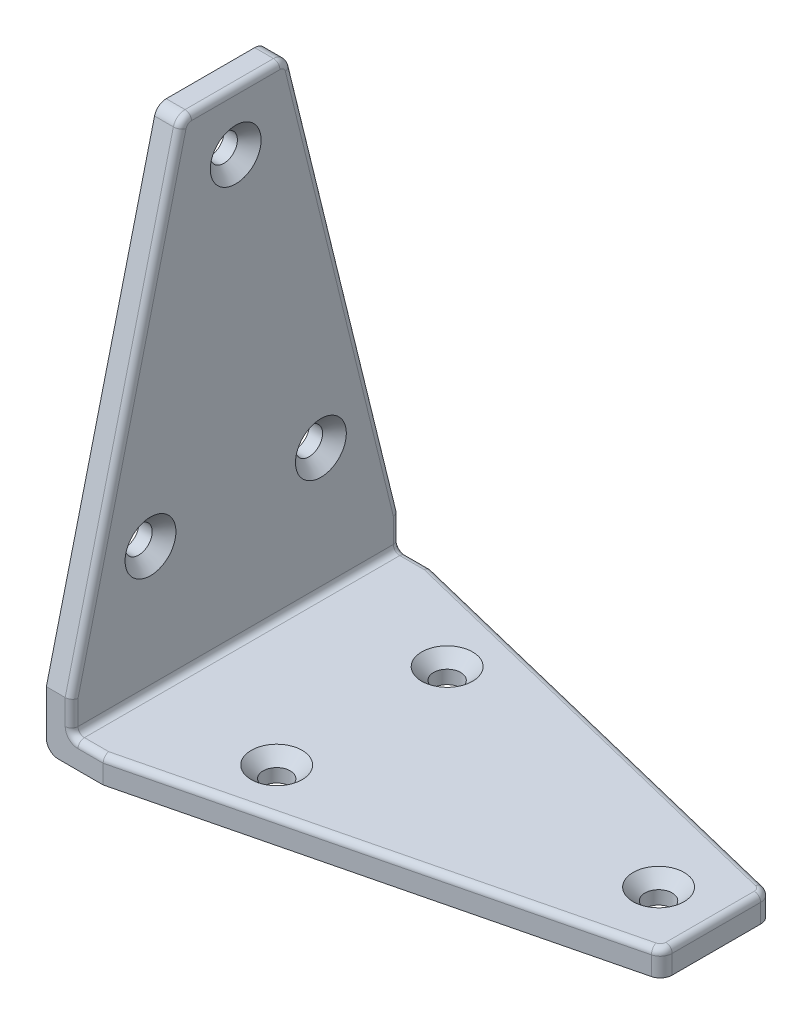
SolidWorks part; units mm, degrees
ref_plane "Front" through (0, 0, 0) normal (0, 0, 1) x (1, 0, 0)
ref_plane "Top" through (0, 0, 0) normal (0, 1, 0) x (1, 0, 0)
ref_plane "Right" through (0, 0, 0) normal (1, 0, 0) x (0, 0, -1)
sketch "Sketch0" plane through (0, 0, 0) normal (0, 0, 1) x (1, 0, 0)
  line L0 (0, 1.905) -> (0, 80.1688) construction
  line L1 (1.905, 0) -> (80.1688, 0) construction
  line L2 (80.1688, 0) -> (80.1688, 4) construction
  arc A0 (1.905, 0) -> (0, 1.905) centre (1.905, 1.905) cw construction
  point P6 (0, 0)
  point P7 (24, 0)
  point P9 (0, 71)
  point P10 (71, 0)
  point P11 (0, 24)
  dimension "D3" = 1.905
  dimension "D1" = 80.1688
  dimension "D2" = 80.1688
  dimension "Thickness" = 4
  dimension "C1" = 71
  dimension "C2" = 24
  dimension "D4" = 24
  dimension "D5" = 71
sketch "Sketch00" plane through (0, 0, 0) normal (0, 1, 0) x (1, 0, 0)
  line L0 (0, 0) -> (80.1688, 0) construction
  line L1 (0, 25.9953) -> (0, -25.9953) construction
  line L3 (1.905, 0) -> (80.1688, 0) construction
  circle A0 centre (71, 0) radius 2.15 construction
  circle A1 centre (71, 0) radius 4.25 construction
  circle A2 centre (24, 13.5) radius 2.15 construction
  circle A3 centre (24, 13.5) radius 4.25 construction
  circle A4 centre (24, -13.5) radius 4.25 construction
  circle A5 centre (24, -13.5) radius 2.15 construction
  point P4 (0, 0)
  point P11 (73.15, 0)
  dimension "Hole Dia" = 4.3
  dimension "D2" = 8.5
  dimension "C4" = 27
  dimension "B" = 51.9906
sketch "Sketch1" plane through (0, 0, 0) normal (0, 0, 1) x (1, 0, 0)
  line L0 (0, 1.905) -> (0, 80.1688)
  line L1 (1.905, 0) -> (80.1688, 0)
  arc A0 (1.905, 0) -> (0, 1.905) centre (1.905, 1.905) cw
  point P6 (0, 0)
extrude "Extrude-Thin2" add sketch "Sketch1" along normal mid plane 51.9906 thin thin type one direction reverse wall 4
sketch "Sketch2" plane through (4, 0, 0) normal (1, 0, 0) x (0, 0, -1)
  line L0 (-8.5, 80.1688) -> (8.5, 80.1688)
  line L1 (-25.9953, 80.1688) -> (25.9953, 80.1688) construction
  line L2 (8.5, 80.1688) -> (25.9953, 9)
  line L3 (25.9953, 80.1688) -> (25.9953, 4) construction
  line L4 (25.9953, 9) -> (38.1, 9)
  line L5 (38.1, 9) -> (38.1, 105.5687)
  line L6 (38.1, 105.5687) -> (-38.1, 105.5687)
  line L7 (-38.1, 105.5687) -> (-38.1, 9)
  line L8 (-38.1, 9) -> (-25.9953, 9)
  line L9 (-25.9953, 80.1688) -> (-25.9953, 4) construction
  line L10 (-25.9953, 9) -> (-8.5, 80.1688)
  line L11 (0, 0) -> (0, 80.1688) construction
  line L12 (-25.9953, 0) -> (25.9953, 0) construction
  dimension "D1" = 17
  dimension "D2" = 9
  dimension "D3" = 76.2
  dimension "D4" = 25.4
extrude "Cut-Extrude1" cut sketch "Sketch2" against normal through all
sketch "Sketch3" plane through (0, 4, 0) normal (0, 1, 0) x (1, 0, 0)
  line L0 (0, 0) -> (80.1687, 0) construction
  line L1 (80.1688, -25.9953) -> (80.1688, 25.9953) construction
  line L2 (9, 25.9953) -> (80.1687, 8.5)
  line L3 (4, 25.9953) -> (80.1688, 25.9953) construction
  line L4 (80.1687, 8.5) -> (80.1687, -8.5)
  line L5 (9, 25.9953) -> (9, 38.1)
  line L6 (9, 38.1) -> (105.5687, 38.1)
  line L7 (105.5687, 38.1) -> (105.5687, -38.1)
  line L8 (9, -38.1) -> (105.5687, -38.1)
  line L9 (9, -25.9953) -> (9, -38.1)
  line L10 (9, -25.9953) -> (80.1687, -8.5)
  line L11 (0, 8.5) -> (0, 25.9953) construction
  point P13 (105.5687, 0)
  dimension "D1" = 17
  dimension "D2" = 9
  dimension "D3" = 76.2
  dimension "D4" = 25.4
extrude "Cut-Extrude2" cut sketch "Sketch3" against normal through all
sketch "Sketch5" plane through (0, 4, 0) normal (0, 1, 0) x (1, 0, 0)
  line L0 (0, 0) -> (80.1687, 0) construction
  line L1 (80.1687, -8.5) -> (80.1687, 8.5) construction
  circle A0 centre (71, 0) radius 2.15
  circle A1 centre (71, 0) radius 4.25 construction
  circle A2 centre (24, 13.5) radius 2.15
  circle A3 centre (24, 13.5) radius 4.25 construction
  circle A4 centre (24, -13.5) radius 4.25 construction
  circle A5 centre (24, -13.5) radius 2.15
  circle A6 centre (24, 13.5) radius 2.15 construction
  circle A7 centre (24, 13.5) radius 4.25 construction
extrude "Cut-Extrude4" cut sketch "Sketch5" against normal through all
sketch "Sketch4" plane through (4, 0, 0) normal (1, 0, 0) x (0, 0, -1)
  line L0 (0, 0) -> (0, 80.1688) construction
  line L2 (0, 0) -> (0, 71) construction
  circle A0 centre (0, 71) radius 2.15
  circle A1 centre (-13.5, 24) radius 2.15
  circle A2 centre (0, 71) radius 4.25 construction
  circle A3 centre (-13.5, 24) radius 4.25 construction
  circle A4 centre (13.5, 24) radius 4.25 construction
  circle A5 centre (13.5, 24) radius 2.15
  dimension "D1" = 4.3
  dimension "D2" = 8.5
extrude "Cut-Extrude3" cut sketch "Sketch4" against normal through all
fillet "Fillet1" radius 1.016 11 edges at (4, 6.5, -25.9953) (6.5, 4, -25.9953) (4, 6.5, 25.9953) (6.5, 4, 25.9953) (80.1687, 4, 0) (44.5844, 4, 17.2477) (44.5844, 4, -17.2477) (4, 44.5844, 17.2477) (4, 44.5844, -17.2477) (4, 80.1688, 0) (4, 4, 0)
fillet "Fillet2" radius 1.905 8 edges at (3.7024, 79.8712, -8.2667) (3.7024, 79.8712, 8.2667) (79.8712, 3.7024, -8.2667) (79.8712, 3.7024, 8.2667) (80.1687, 1.492, 8.5) (80.1687, 1.492, -8.5) (1.492, 80.1688, 8.5) (1.492, 80.1688, -8.5)
chamfer "Chamfer1" distance 1.8796 angle 45 6 edges at (71, 4, 2.15) (24, 4, -11.35) (4, 24, 11.35) (4, 71, -2.15) (4, 24, -11.35) (24, 4, 11.35)
equation "\"D4@Sketch0\" = \"C2@Sketch0\""
equation "\"D5@Sketch0\" = \"C1@Sketch0\""
equation "\"D5@Extrude-Thin2\" = \"Thickness@Sketch0\""
equation "\"D1@Sketch4\"=\"Hole Dia@Sketch00\""
equation "\"D2@Sketch4\"=\"D2@Sketch00\""
equation "\"D1@Extrude-Thin2\"=\"B@Sketch00\""
